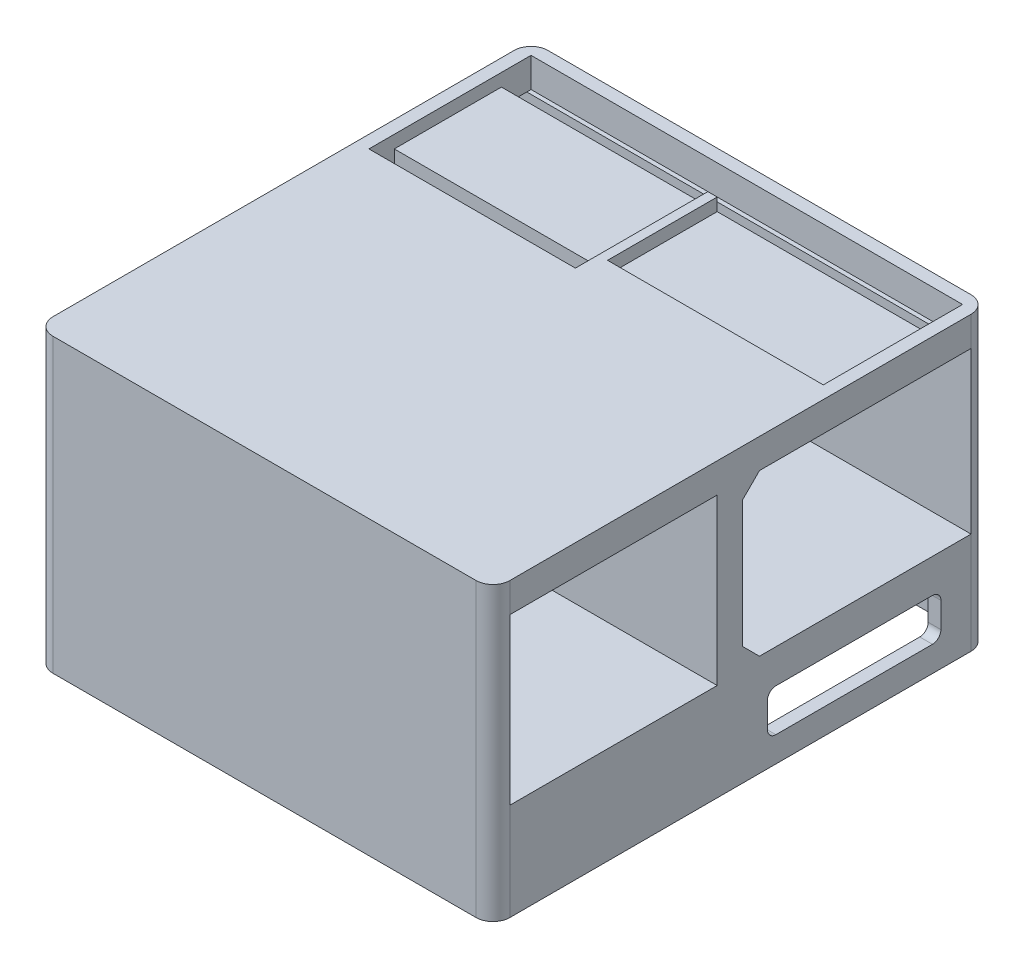
SolidWorks part; units mm, degrees
note: The reader was unsure of these and kept them because the rebuilt part matched: shared geometry of "Sketch3<3>", "Sketch3<5>".
ref_plane "前视基准面" through (0, 0, 0) normal (0, 0, 1) x (1, 0, 0)
ref_plane "上视基准面" through (0, 0, 0) normal (0, 1, 0) x (1, 0, 0)
ref_plane "右视基准面" through (0, 0, 0) normal (1, 0, 0) x (0, 0, -1)
sketch "Sketch3" plane through (0, 0, 0) normal (0, 1, 0) x (1, 0, 0)
  line L0 (-27, 15) -> (-27, 16.5)
  line L1 (-25.5, 12) -> (25.5, 12)
  line L2 (-25.5, 12) -> (-25.5, -10)
  line L3 (-23.5, -12) -> (23.5, -12)
  line L4 (25.5, 12) -> (25.5, -10)
  line L5 (-25.5, 12) -> (25.5, -12) construction
  line L6 (-25.5, -12) -> (25.5, 12) construction
  line L7 (-25.5, 12) -> (25.5, 12)
  line L8 (-25.5, 12) -> (-25.5, 13)
  line L9 (-23.5, 15.5) -> (23.5, 15.5)
  line L10 (25.5, 12) -> (25.5, 13)
  line L11 (-23.5, 15.5) -> (23.5, 15.5)
  line L12 (-27, 13) -> (-27, -11.5)
  line L13 (-25, -13.5) -> (25, -13.5)
  line L14 (27, 13) -> (27, -11.5)
  line L15 (-25, 17) -> (25, 17)
  line L16 (27, 16.5) -> (27, 15)
  line L17 (27, 15) -> (27, 13)
  line L18 (23.5, 15.5) -> (0, 15.5)
  line L19 (25.5, 13) -> (25.5, -0.5)
  line L22 (-25.5, 12) -> (-1.1, 12)
  line L23 (-25.5, 12) -> (-25.5, -3.66)
  line L24 (-25.5, -3.66) -> (-1.1, -3.66)
  line L25 (-1.1, 12) -> (-1.1, -3.66)
  line L30 (0, 12) -> (25.5, 12)
  line L31 (0, 12) -> (0, -0.96)
  line L32 (0, -0.96) -> (25.5, -0.96)
  line L33 (25.5, 12) -> (25.5, -0.96)
  line L34 (-27, 15) -> (-27, 13)
  line L35 (-25.5, -0.66) -> (-1.1, -0.66)
  line L36 (-23.5, 15.5) -> (-25.5, 15.5)
  line L37 (-25.5, 15.5) -> (-25.5, 13)
  line L38 (25.5, 13) -> (25.5, 15.5)
  line L39 (25.5, 15.5) -> (23.5, 15.5)
  line L40 (-27, -11.5) -> (-27, -39.5)
  line L41 (-25, -41.5) -> (25, -41.5)
  line L42 (27, -11.5) -> (27, -39.5)
  line L43 (27, -39.5) -> (25.5, -39.5)
  line L45 (-25, -13.5) -> (25, -13.5)
  line L46 (-25, -13.5) -> (-25, -38)
  line L47 (-25, -38) -> (25, -38)
  line L48 (25, -13.5) -> (25, -38)
  arc A2 (-27, -11.5) -> (-25, -13.5) centre (-25, -11.5) ccw
  arc A3 (27, -11.5) -> (25, -13.5) centre (25, -11.5) cw
  arc A6 (-25.5, -10) -> (-23.5, -12) centre (-23.5, -10) ccw
  arc A7 (23.5, -12) -> (25.5, -10) centre (23.5, -10) ccw
  arc A8 (-27, 15) -> (-25, 17) centre (-25, 15) cw
  arc A9 (27, 15) -> (25, 17) centre (25, 15) ccw
  arc A10 (25, -41.5) -> (27, -39.5) centre (25, -39.5) ccw
  arc A11 (-25, -41.5) -> (-27, -39.5) centre (-25, -39.5) cw
  point P0 (0, 0)
  point P34 (-25.5, 15.5)
  dimension "D12" = 2
  dimension "D16" = 2
  dimension "D1" = 51
  dimension "D2" = 24
  dimension "D3" = 3.5
  dimension "D4" = 1.5
  dimension "D5" = 1.5
  dimension "D6" = 1.5
  dimension "D7" = 1.5
  dimension "D8" = 12.96
  dimension "D9" = 25.5
  dimension "D10" = 15.66
  dimension "D11" = 24.4
  dimension "D13" = 3
  dimension "D14" = 28
  dimension "D15" = 24.5
extrude "Boss-Extrude4" add sketch "Sketch3" against normal blind 21 contours L16 L15 L0 L11 L9 | L14 L11 L10 L4 L3 L2 L8 L12 L13 | L25 L1 L2 L24 | L31 L32 L4 L1 | L32 L31 L7 L25 L24 L2 L3 L4 | L35 L23 L24 L25 | A11 L41 A10 L42 A3 L48 L47 L46 A2 L40 | L48 L13 L46 L47
extrude "Boss-Extrude5" add sketch "Sketch3<3>" along normal blind 3.5
sketch "Sketch3<3>" plane through (0, 0, 0) normal (0, 1, 0) x (1, 0, 0) same geometry as "Sketch3"
sketch "Sketch4" plane through (-27, 0, 0) normal (-1, 0, 0) x (0, 0, 1)
  line L5 (-15, 0) -> (12, 0)
  line L6 (-15, 0) -> (-15, -19)
  line L7 (-15, -19) -> (12, -19)
  line L8 (12, 0) -> (12, -19)
  line L9 (-15, 0) -> (12, -19) construction
  line L10 (-15, -19) -> (12, 0) construction
  point P6 (-1.5, -9.5)
extrude "Cut-Extrude4" cut sketch "Sketch4" against normal through all
extrude "Boss-Extrude6" add sketch "Sketch3<5>" along normal blind 2 contours L2 L35 L25 L1 | L31 L32 L4 L1
sketch "Sketch3<5>" plane through (0, 0, 0) normal (0, 1, 0) x (1, 0, 0) same geometry as "Sketch3"
sketch "Sketch5" plane through (0, -21, 0) normal (0, -1, 0) x (1, 0, 0)
  line L1 (-25.5, 13.5) -> (25.5, 13.5)
  line L3 (-25.5, -16.5) -> (25.5, -16.5)
  line L5 (25.5, -16.5) -> (25.5, 13.5)
  line L6 (-25.5, -16.5) -> (-25.5, 13.5)
extrude "Boss-Extrude7" add sketch "Sketch5" along normal blind 10
sketch "Sketch6" plane through (-27, 0, 0) normal (-1, 0, 0) x (0, 0, 1)
  line L0 (39.5, -31) -> (-15, -31) construction
  line L1 (-10.4388, -23) -> (8.0612, -23)
  line L2 (-11.4388, -24) -> (-11.4388, -27)
  line L3 (-10.4388, -28) -> (8.0612, -28)
  line L4 (9.0612, -24) -> (9.0612, -27)
  line L5 (-11.4388, -23) -> (9.0612, -28) construction
  line L6 (-11.4388, -28) -> (9.0612, -23) construction
  arc A0 (-11.4388, -24) -> (-10.4388, -23) centre (-10.4388, -24) cw
  arc A1 (8.0612, -23) -> (9.0612, -24) centre (8.0612, -24) cw
  arc A2 (9.0612, -27) -> (8.0612, -28) centre (8.0612, -27) cw
  arc A3 (-10.4388, -28) -> (-11.4388, -27) centre (-10.4388, -27) cw
  point P0 (-1.1888, -25.5)
  dimension "D4" = 1
  dimension "D1" = 3
  dimension "D2" = 20.5
  dimension "D3" = 5
extrude "Cut-Extrude5" cut sketch "Sketch6" against normal through all
sketch "Sketch8" plane through (27, 0, 0) normal (1, 0, 0) x (0, 0, -1)
  line L0 (29.7, 0) -> (-29.7, 0) construction
  line L1 (-15, 0) -> (-39.5, 0)
  line L2 (-15, 0) -> (-15, -19.5)
  line L3 (-15, -19.5) -> (-39.5, -19.5)
  line L4 (-39.5, 0) -> (-39.5, -19.5)
  line L5 (-39.5, -31) -> (-39.5, 3.5) construction
  dimension "D1" = 0
  dimension "D2" = 24.5
  dimension "D3" = 19.5
extrude "Cut-Extrude6" cut sketch "Sketch8" against normal up to next
chamfer "Chamfer1" distance 2 angle 45 10 edges at (25.5, -26, 13.5) (-25.5, -26, 13.5) (-25.5, -26, -16.5) (25.5, -26, -16.5) (-25.5, -21, -1.5) (0, -21, 13.5) (25.5, -21, -1.5) (0, -21, -16.5) (0, 0, 12) (0, -19, 12)
